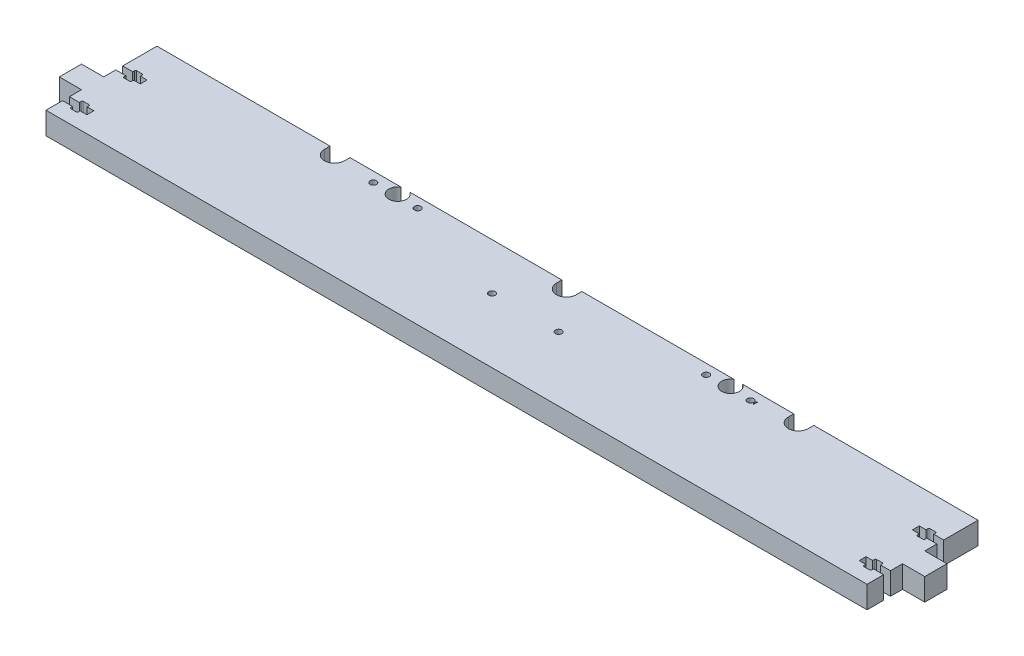
SolidWorks part; units mm, degrees
ref_plane "Front Plane" through (0, 0, 0) normal (0, 0, 1) x (1, 0, 0)
ref_plane "Top Plane" through (0, 0, 0) normal (0, 1, 0) x (1, 0, 0)
ref_plane "Right Plane" through (0, 0, 0) normal (1, 0, 0) x (0, 0, -1)
sketch "Sketch1" plane through (0, 0, 0) normal (0, 1, 0) x (1, 0, 0)
  line L0 (0, 25) -> (0, -25)
  line L1 (-185, 25) -> (0, 25)
  line L2 (-185, 25) -> (-185, -25) construction
  line L3 (-185, -25) -> (0, -25)
  line L4 (-185, -4) -> (-195, -4) construction
  line L5 (-185, 25) -> (0, 0) construction
  line L6 (-185, -25) -> (0, 0) construction
  line L7 (-185, -9) -> (-195, -9)
  line L8 (-195, -9) -> (-195, 1)
  line L9 (-195, 1) -> (-185, 1)
  line L10 (-185, 1) -> (-185, 25)
  line L11 (-185, -9) -> (-185, -25)
  line L47 (0, -25) -> (0, 25) construction
  line L89 (0, -25) -> (0, 25) construction
  point P0 (0, 0)
  dimension "D1" = 185
  dimension "D25" = 25
  dimension "D4" = 50
  dimension "D3" = 21
  dimension "D5" = 10
  dimension "D6" = 10
  dimension "D7" = 5
extrude "MainBody" add sketch "Sketch1" along normal blind 10 contours L3 region at (-93.5428, 0, 0.0428)
sketch "Sketch5" plane through (0, 10, 0) normal (0, 1, 0) x (1, 0, 0)
  line L0 (-185, 8) -> (-174, 8) construction
  line L1 (-185, 1) -> (-185, 25) construction
  line L2 (-185, 9.55) -> (-174, 9.55) construction
  line L3 (-174, 9.55) -> (-174, 6.45) construction
  line L4 (-174, 6.45) -> (-185, 6.45) construction
  line L5 (-185, 9.55) -> (-180.5, 9.55)
  line L6 (-180.5, 9.55) -> (-180.5, 10.35)
  line L7 (-180, 10.85) -> (-177.5, 10.85)
  line L8 (-177, 10.35) -> (-177, 9.55)
  line L9 (-177, 9.55) -> (-174, 9.55)
  line L10 (-174, 9.55) -> (-174, 6.45)
  line L11 (-185, 6.45) -> (-185, 9.55)
  line L12 (-195, -9) -> (-195, 1) construction
  line L13 (-185, 6.45) -> (-174, 6.45) construction
  line L14 (-177, 6.45) -> (-174, 6.45)
  line L15 (-177, 5.65) -> (-177, 6.45)
  line L16 (-180, 5.15) -> (-177.5, 5.15)
  line L17 (-180.5, 6.45) -> (-180.5, 5.65)
  line L18 (-185, 6.45) -> (-180.5, 6.45)
  line L19 (-185, 1) -> (-185, -9) construction
  line L20 (-195, -4) -> (-185, -4) construction
  line L21 (-195, -9) -> (-195, 1) construction
  line L22 (-185, -14.45) -> (-174, -14.45) construction
  line L23 (-174, -14.45) -> (-185, -14.45) construction
  line L24 (-174, -17.55) -> (-174, -14.45) construction
  line L25 (-185, -17.55) -> (-174, -17.55) construction
  line L26 (-185, -16) -> (-174, -16) construction
  line L27 (-185, -14.45) -> (-180.5, -14.45)
  line L28 (-180.5, -14.45) -> (-180.5, -13.65)
  line L29 (-180, -13.15) -> (-177.5, -13.15)
  line L30 (-177, -13.65) -> (-177, -14.45)
  line L31 (-177, -14.45) -> (-174, -14.45)
  line L32 (-185, -14.45) -> (-185, -17.55)
  line L33 (-174, -17.55) -> (-174, -14.45)
  line L34 (-177, -17.55) -> (-174, -17.55)
  line L35 (-177, -18.35) -> (-177, -17.55)
  line L36 (-180, -18.85) -> (-177.5, -18.85)
  line L37 (-180.5, -17.55) -> (-180.5, -18.35)
  line L38 (-185, -17.55) -> (-180.5, -17.55)
  line L39 (-185, 6.45) -> (-174, 6.45) construction
  arc A0 (-177.5, 10.85) -> (-177, 10.35) centre (-177.5, 10.35) cw
  arc A1 (-180.5, 10.35) -> (-180, 10.85) centre (-180, 10.35) cw
  arc A2 (-180.5, 5.65) -> (-180, 5.15) centre (-180, 5.65) ccw
  arc A3 (-177.5, 5.15) -> (-177, 5.65) centre (-177.5, 5.65) ccw
  arc A4 (-177.5, -13.15) -> (-177, -13.65) centre (-177.5, -13.65) cw
  arc A5 (-180.5, -13.65) -> (-180, -13.15) centre (-180, -13.65) cw
  arc A6 (-180.5, -18.35) -> (-180, -18.85) centre (-180, -18.35) ccw
  arc A7 (-177.5, -18.85) -> (-177, -18.35) centre (-177.5, -18.35) ccw
  point P6 (-195, -4)
  point P17 (-177, 10.85)
  point P20 (-180.5, 10.85)
  point P29 (-180.5, 5.15)
  point P30 (-177, 5.15)
  point P61 (-177, -13.15)
  point P62 (-180.5, -13.15)
  point P63 (-180.5, -18.85)
  point P64 (-177, -18.85)
  dimension "D8" = 0.5
  dimension "D1" = 11
  dimension "D2" = 1.55
  dimension "D4" = 3.5
  dimension "D5" = 8
  dimension "D6" = 2.85
  dimension "D7" = 12
extrude "ScrewCutouts" cut sketch "Sketch5" against normal through all
mirror "Mirror1" about plane through (0, 0, 0) normal (1, 0, 0) of "ScrewCutouts", "MainBody"
sketch "Sketch3" plane through (0, 10, 0) normal (0, 1, 0) x (1, 0, 0)
  line L0 (2, 25) -> (2, -25) construction
  line L1 (-185, 25) -> (185, 25) construction
  line L2 (-185, -25) -> (185, -25) construction
  line L3 (-63, 20.5) -> (-83, 20.5) construction
  line L4 (-73, 17.5) -> (-73, 25.5) construction
  line L5 (77, 17.5) -> (77, 25.5) construction
  line L6 (67, 20.5) -> (87, 20.5) construction
  circle A0 centre (-73, 21.5) radius 4
  circle A1 centre (-83, 20.5) radius 1.45
  circle A2 centre (-63, 20.5) radius 1.45
  circle A3 centre (67, 20.5) radius 1.45
  circle A4 centre (87, 20.5) radius 1.45
  circle A5 centre (77, 21.5) radius 4
  dimension "D2" = 8
  dimension "D4" = 2.9
  dimension "D1" = 3.5
  dimension "D5" = 75
  dimension "D6" = 2
  dimension "D3" = 10
  dimension "D7" = 1
extrude "RodCutouts" cut sketch "Sketch3" against normal through all
sketch "Sketch6" plane through (0, 10, 0) normal (0, 1, 0) x (1, 0, 0)
  line L0 (-73, 21.5) -> (77, 21.5) construction
  line L1 (2, 21.5) -> (2, -25) construction
  line L2 (-185, -25) -> (185, -25) construction
  line L3 (17, 4) -> (-13, 4) construction
  line L4 (-71.0635, 25) -> (75.0635, 25) construction
  circle A0 centre (-13, 4) radius 1.45
  circle A1 centre (17, 4) radius 1.45
  point P13 (2, 4)
  dimension "D3" = 21
  dimension "D1" = 2.9
  dimension "D2" = 15
extrude "Cut-Extrude1" cut sketch "Sketch6" against normal through all
sketch "Sketch7" plane through (0, 10, 0) normal (0, 1, 0) x (1, 0, 0)
  line L0 (-73, 21.5) -> (77, 21.5) construction
  line L1 (2, 21.5) -> (2, -25) construction
  line L3 (-102.5, 25) -> (-102.5, 22.5) construction
  line L4 (-185, 25) -> (-74.9365, 25) construction
  line L5 (-98, 25) -> (-98, 22.5)
  line L6 (-107, 25) -> (-107, 22.5)
  line L7 (106.5, 25) -> (106.5, 22.5) construction
  line L8 (102, 25) -> (102, 22.5)
  line L9 (111, 25) -> (111, 22.5)
  line L12 (-185, -25) -> (185, -25) construction
  arc A0 (-98, 25) -> (-107, 25) centre (-102.5, 25) ccw
  arc A1 (-107, 22.5) -> (-98, 22.5) centre (-102.5, 22.5) ccw
  arc A2 (102, 25) -> (111, 25) centre (106.5, 25) cw
  arc A3 (111, 22.5) -> (102, 22.5) centre (106.5, 22.5) cw
  point P12 (-102.5, 23.75)
  point P19 (106.5, 23.75)
  dimension "D1" = 4.5
  dimension "D2" = 2.5
  dimension "D3" = 104.5
extrude "BedAdjustmentScrewCutout" cut sketch "Sketch7" against normal through all
sketch "Sketch8" plane through (0, 10, 0) normal (0, 1, 0) x (1, 0, 0)
  line L0 (88.25, 20.5) -> (89.25, 20.5) construction
  line L1 (88.45, 20.5) -> (88.45, 25) construction
  line L2 (88.25, 20.5) -> (89.25, 21.5)
  line L3 (89.25, 21.5) -> (89.25, 19.5)
  line L4 (88.25, 20.5) -> (89.25, 19.5)
  line L5 (78.9365, 25) -> (102, 25) construction
  circle A1 centre (87, 20.5) radius 1.45 construction
  point P9 (89.25, 20.5)
  dimension "D1" = 1
  dimension "D2" = 1
  dimension "D3" = 0.2
extrude "DirectionKey" cut sketch "Sketch8" against normal through all
sketch "Sketch9" plane through (0, 10, 0) normal (0, 1, 0) x (1, 0, 0)
  line L0 (-13, 4) -> (17, 4) construction
  line L1 (2, 4) -> (2, 25) construction
  line L2 (-71.0635, 25) -> (75.0635, 25) construction
  line L3 (2, 27.5) -> (2, 22.5) construction
  line L4 (6.5, 27.5) -> (6.5, 22.5)
  line L5 (-2.5, 27.5) -> (-2.5, 22.5)
  arc A0 (6.5, 27.5) -> (-2.5, 27.5) centre (2, 27.5) ccw
  arc A1 (-2.5, 22.5) -> (6.5, 22.5) centre (2, 22.5) ccw
  arc A2 (-107, 22.5) -> (-98, 22.5) centre (-102.5, 22.5) ccw construction
  point P10 (2, 25)
  dimension "D2" = 2.5
extrude "Cut-Extrude2" cut sketch "Sketch9" against normal through all
equation "\"Y-ROD-SPACING\"=75"
equation "\"Y-BED-OFFSET\"=2"
equation "\"T-SLOT-NUT-FILLET-RADIUS\"=0.5"
equation "\"T-SLOT-SCREW-SHAFT-RADIUS\"=1.55"
equation "\"T-SLOT-SCREW-SHAFT-CUTOUT-LENGTH\"=11"
equation "\"T-SLOT-NUT-DEPTH\"=3.5"
equation "\"T-SLOT-NUT-WIDTH\"=2.85"
equation "\"T-SLOT-NUT-END-DISTANCE\"=8"
equation "\"ACRYLIC-TAB-CUTOUT-SIZE\"=\"ACRYLIC-THICKNESS\"+\"ACRYLIC-TAB-TOLERANCE\"*2"
equation "\"ACRYLIC-M3-HOLE\"=2.9"
equation "\"D1@Sketch5\"=\"T-SLOT-SCREW-SHAFT-CUTOUT-LENGTH\""
equation "\"D2@Sketch5\"=\"T-SLOT-SCREW-SHAFT-RADIUS\""
equation "\"D4@Sketch5\"=\"T-SLOT-NUT-DEPTH\""
equation "\"D5@Sketch5\"=\"T-SLOT-NUT-END-DISTANCE\""
equation "\"D6@Sketch5\"=\"T-SLOT-NUT-WIDTH\""
equation "\"D8@Sketch5\"=\"T-SLOT-NUT-FILLET-RADIUS\""
equation "\"D4@Sketch3\"=\"ACRYLIC-M3-HOLE\""
equation "\"D5@Sketch3\"=\"Y-ROD-SPACING\""
equation "\"D6@Sketch3\"=\"Y-BED-OFFSET\""
equation "\"Y-BED-ROD-INSET\"=3.5"
equation "\"D1@Sketch3\"=\"Y-BED-ROD-INSET\""
equation "\"SMOOTHROD-CAP-SCREW-DISTANCE\"=20"
equation "\"D3@Sketch3\"=\"SMOOTHROD-CAP-SCREW-DISTANCE\"/2"
equation "\"ACRYLIC-TAB-WIDTH\"=\"ACRYLIC-THICKNESS\""
equation "\"FRAME-WIDTH-INNER\"=370"
equation "\"D6@Sketch1\"=\"ACRYLIC-TAB-WIDTH\""
equation "\"D5@Sketch1\"=\"ACRYLIC-TAB-WIDTH\""
equation "\"D1@Sketch1\"=\"FRAME-WIDTH-INNER\"/2"
equation "\"X-ROD-SPACING\"=45"
equation "\"Z-ROD-SPACING\"=17.5"
equation "\"ACRYLIC-THICKNESS\"=10"
equation "\"ACRYLIC-THICKNESS2\"=4.5"
equation "\"NEMA17-HOLE-SPACING\"=31"
equation "\"NEMA17-CENTRAL-CUTOUT\"=22.5"
equation "\"Z-BRACKET-REACH\"=57"
equation "\"TOP-BRACKET-SPACING\"=40"
equation "\"SMOOTHROD-X-LENGTH\"=350"
equation "\"SMOOTHROD-Y-LENGTH\"=350"
equation "\"SMOOTHROD-Z-LENGTH\"=350"
equation "\"SMOOTHROD-TIGHTENING-HEADROOM\"=.25"
equation "\"LEADSCREW-Z-LENGTH\"=300"
equation "\"SCREW-LENGTH-FRAME\"=\"ACRYLIC-THICKNESS\" + 10"
equation "\"SCREW-HEAD-RADIUS\"=6"
equation "\"PRINTED-X-SMOOTHROD-DIAMETER\"=8.8"
equation "\"PRINTED-X-SMOOTHROD-CUTOUT\"=10"
equation "\"PRINTED-X-BASE-HEIGHT\"=10"
equation "\"PRINTED-LM8UU-CUTOUT-SIZE\"=15.5"
equation "\"PRINTED-LM8UU-CUTOUT-LENGTH\"=24.5"
equation "\"PRINTED-X-IDLER-HEIGHT\"=16"
equation "\"PSU-MOUNTING-WIDTH\"=95"
equation "\"PSU-MOUNTING-HEIGHT\"=177"
equation "\"D1@MainBody\"=\"ACRYLIC-THICKNESS\""
equation "\"D7@Sketch1\"=\"ACRYLIC-TAB-WIDTH\"/2"
equation "\"D1@Sketch6\"=\"ACRYLIC-M3-HOLE\""
equation "\"Y-BELT-TO-ROD-DISTANCE\"=20"
equation "\"Y-BED-SCREW-SPACING\"=209"
equation "\"Z-ROD-INSET\"=13.5"
equation "\"SPOOL-HOLDER-ROD-SPACING\"=150"
equation "\"D3@Sketch7\"=\"Y-BED-SCREW-SPACING\"/2"
equation "\"Y-BED-SCREW-CUTOUT-SLOT-HEIGHT\"=2.5"
equation "\"D2@Sketch7\"=\"Y-BED-SCREW-CUTOUT-SLOT-HEIGHT\""
equation "\"ACRYLIC-TAB-TOLERANCE\"=-.05"
equation "\"SCREW-LENGTH-MOTOR\"=\"ACRYLIC-THICKNESS\" + 5"
equation "\"SCREW-LENGTH-EXTRUDER\"=28"
equation "\"PRINTED-M3-HOLE\"=3.5"
equation "\"ACRYLIC-X-CARRIAGE-WIDTH\"=55"
equation "\"ACRYLIC-X-CARRIAGE-HEIGHT\"=75"
equation "\"ACRYLIC-X-CARRIAGE-LM8UU-CUTOUT-WIDTH\"=24.25"
equation "\"ACRYLIC-X-CARRIAGE-LM8UU-CUTOUT-HEIGHT\"=11.0"
equation "\"ACRYLIC-X-CARRIAGE-SCREW-SPACING-X\"=15"
equation "\"ACRYLIC-X-CARRIAGE-SCREW-SPACING-Y\"=33"
equation "\"ACRYLIC-X-CARRIAGE-CENTER-TAB-SPACING\"=14"
equation "\"ACRYLIC-X-CARRIAGE-EXTRUDER-OFFSET\"=26"
equation "\"ACRYLIC-X-CARRIAGE-EXTRUDER-ANGLE\"=90"
equation "\"ACRYLIC-X-CARRIAGE-EXTRUDER-SHELF-DEPTH\"=\"ACRYLIC-X-CARRIAGE-EXTRUDER-OFFSET\" + 28"
equation "\"ACRYLIC-X-CARRIAGE-EXTRUDER-BRACE-SPACING\"=23"
equation "\"ACRYLIC-X-CARRIAGE-EXTRUDER-BRACE-TAB-OFFSET\"=20"
equation "\"ACRYLIC-X-CARRIAGE-EXTRUDER-BRACE-HEIGHT\"=35"
equation "\"ACRYLIC-X-CARRIAGE-EXTRUDER-BRACE-SCREW-SPACING\"=22"
equation "\"ACRYLIC-X-CARRIAGE-DUAL-WIDTH-MULTIPLIER\"=1.65"
equation "\"ACRYLIC-X-CARRIAGE-DUAL-HOTEND-SPACING\"=42"
equation "\"ACRYLIC-X-CARRIAGE-DUAL-WIDTH\"=75"
equation "\"ACRYLIC-X-CARRIAGE-DUAL-HOTEND-SEPARATION\"=36"
equation "\"ACRYLIC-X-CARRIAGE-DUAL-MOUNT-PLATE-DEPTH\"=75"
equation "\"ACRYLIC-X-CARRIAGE-DUAL-MOUNT-BRACE-WIDTH\"=33"
equation "\"ACRYLIC-X-CARRIAGE-DUAL-MOUNT-SCREW-WIDTH\"=40"
equation "\"BLOWER-FAN-WIDTH\"=15"
equation "\"D2@Sketch9\"=\"Y-BED-SCREW-CUTOUT-SLOT-HEIGHT\""
